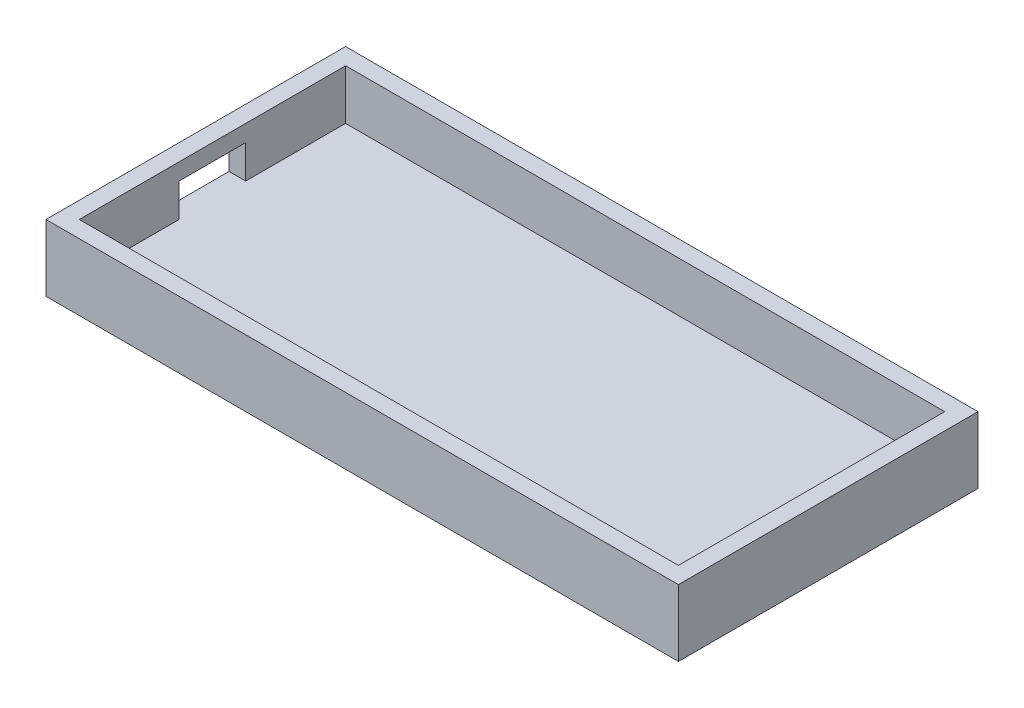
SolidWorks part; units mm, degrees
ref_plane "Front Plane" through (0, 0, 0) normal (0, 0, 1) x (1, 0, 0)
ref_plane "Top Plane" through (0, 0, 0) normal (0, 1, 0) x (1, 0, 0)
ref_plane "Right Plane" through (0, 0, 0) normal (1, 0, 0) x (0, 0, -1)
sketch "Sketch3" plane through (0, 0, 0) normal (0, 1, 0) x (1, 0, 0)
  line L0 (-90, 5) -> (-20, 5)
  line L1 (-90, 40) -> (90, 40)
  line L2 (-90, 40) -> (-90, -40)
  line L3 (-90, -40) -> (90, -40)
  line L4 (90, 40) -> (90, -40)
  line L5 (-90, 40) -> (90, -40) construction
  line L6 (-90, -40) -> (90, 40) construction
  line L7 (-95, 45) -> (95, 45)
  line L8 (-95, 45) -> (-95, -45)
  line L9 (-95, -45) -> (95, -45)
  line L10 (95, 45) -> (95, -45)
  line L11 (-95, 45) -> (95, -45) construction
  line L12 (-95, -45) -> (95, 45) construction
  line L13 (90, -40) -> (65, -40)
  line L14 (90, -40) -> (90, -15)
  line L15 (90, -15) -> (65, -15)
  line L16 (65, -40) -> (65, -15)
  line L17 (-20, 40) -> (-20, 5)
  line L19 (-20, 5) -> (-5, 5)
  line L20 (-20, 5) -> (-20, -5)
  line L21 (-20, -5) -> (-5, -5)
  line L22 (-5, 5) -> (-5, -5)
  circle A0 centre (75.2368, 26.8838) radius 7.5
  point P0 (0, 0)
  point P6 (0, 0)
  point P23 (-20, 5)
  dimension "D8" = 15
  dimension "D1" = 190
  dimension "D2" = 90
  dimension "D3" = 80
  dimension "D4" = 80
  dimension "D5" = 180
  dimension "D6" = 25
  dimension "D7" = 25
  dimension "D9" = 70
  dimension "D10" = 35
  dimension "D11" = 15
  dimension "D12" = 10
extrude "Boss-Extrude2" add sketch "Sketch3" along normal blind 20 contours L10 L7 L8 L9 L1 L4 L3 L2 region at (0, 0, -42.8976)
extrude "Boss-Extrude3" add sketch "Sketch3<4>" along normal blind 5 contours L19 L22 L21 L20 L0 L2 L3 L16 L15 L4 L1 L17 A0 | L22 L19 L20 L21 | L17 L1 L2 L0 | L16 L3 L4 L15 | A0 region at (-55, 0, -22.5) region at (-12.5, 0, 0) region at (6.8094, 0, 3.8814) region at (77.5, 0, 27.5) region at (75.2368, 0, -26.8838)
sketch "Sketch3<4>" plane through (0, 0, 0) normal (0, 1, 0) x (1, 0, 0) same geometry as "Sketch3"
sketch "Sketch4" plane through (-95, 0, 0) normal (-1, 0, 0) x (0, 0, 1)
  line L0 (0, 0) -> (0, 20)
  line L1 (-45, 0) -> (45, 0) construction
  line L2 (-45, 20) -> (45, 20) construction
  line L3 (0, 20) -> (0, 10)
  line L5 (-10, 15) -> (10, 15)
  line L6 (-10, 15) -> (-10, 5)
  line L7 (-10, 5) -> (10, 5)
  line L8 (10, 15) -> (10, 5)
  line L9 (-10, 15) -> (10, 5) construction
  line L10 (-10, 5) -> (10, 15) construction
  dimension "D1" = 20
  dimension "D2" = 10
extrude "Cut-Extrude1" cut sketch "Sketch4" against normal blind 5 contours L6 L7 L0 L5 | L8 L5 L0 L7 region at (-95, 10, -5) region at (-95, 10, 5)
